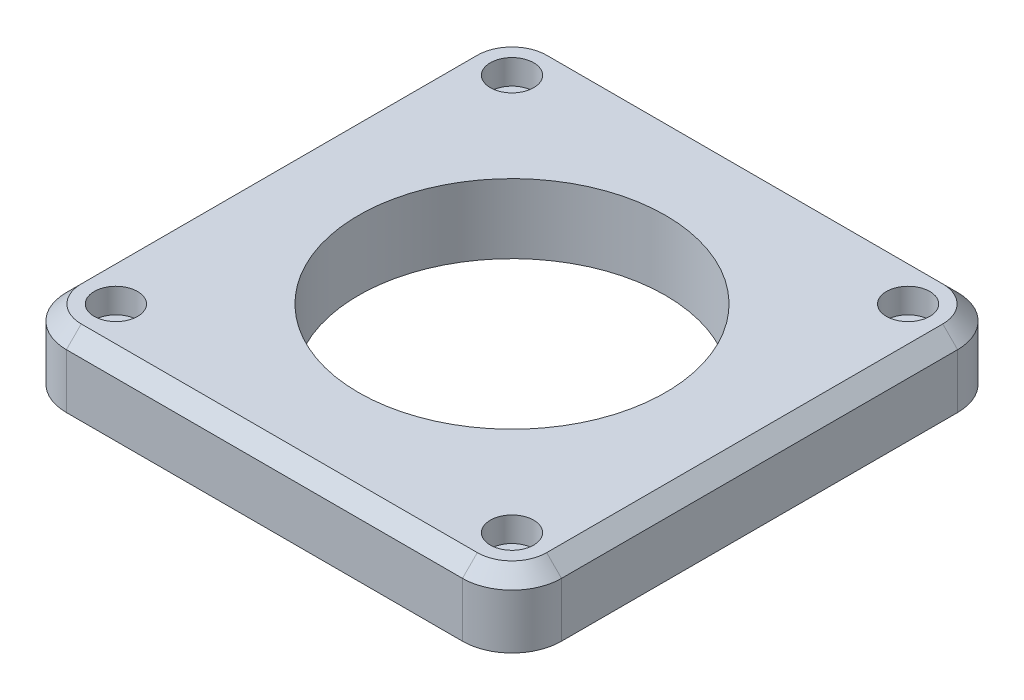
SolidWorks part; units mm, degrees
ref_plane "Front Plane" through (0, 0, 0) normal (0, 0, 1) x (1, 0, 0)
ref_plane "Top Plane" through (0, 0, 0) normal (0, 1, 0) x (1, 0, 0)
ref_plane "Right Plane" through (0, 0, 0) normal (1, 0, 0) x (0, 0, -1)
sketch "Sketch1" plane through (0, 0, 0) normal (0, 1, 0) x (1, 0, 0)
  line L1 (-40, -50) -> (40, -50)
  line L2 (-50, -40) -> (-50, 40)
  line L3 (-40, 50) -> (40, 50)
  line L4 (50, -40) -> (50, 40)
  line L5 (-50, -50) -> (50, 50) construction
  line L6 (-50, 50) -> (50, -50) construction
  circle A0 centre (0, 0) radius 31
  arc A1 (-40, -50) -> (-50, -40) centre (-40, -40) cw
  arc A2 (40, -50) -> (50, -40) centre (40, -40) ccw
  arc A3 (40, 50) -> (50, 40) centre (40, 40) cw
  arc A4 (-50, 40) -> (-40, 50) centre (-40, 40) cw
  circle A5 centre (-40, -40) radius 2.625
  circle A6 centre (40, -40) radius 2.625
  circle A7 centre (40, 40) radius 2.625
  circle A8 centre (-40, 40) radius 2.625
  point P0 (0, 0)
  dimension "D3" = 62
  dimension "D4" = 10
  dimension "D5" = 5.25
  dimension "D1" = 100
  dimension "D2" = 100
extrude "Boss-Extrude1" add sketch "Sketch1" along normal blind 14
sketch "Sketch2" plane through (0, 14, 0) normal (0, 1, 0) x (1, 0, 0)
  circle A0 centre (-40, 40) radius 4.375
  circle A1 centre (40, 40) radius 4.375
  circle A2 centre (40, -40) radius 4.375
  circle A3 centre (-40, -40) radius 4.375
  dimension "D1" = 8.75
extrude "Cut-Extrude1" cut sketch "Sketch2" against normal blind 5
fillet "Chamfer1" radius 3 1 edges at (0, 14, 50) type face fillet profile chamfer first side face at (-40, 14, 44.375) second side face at (0, 7, 50)
